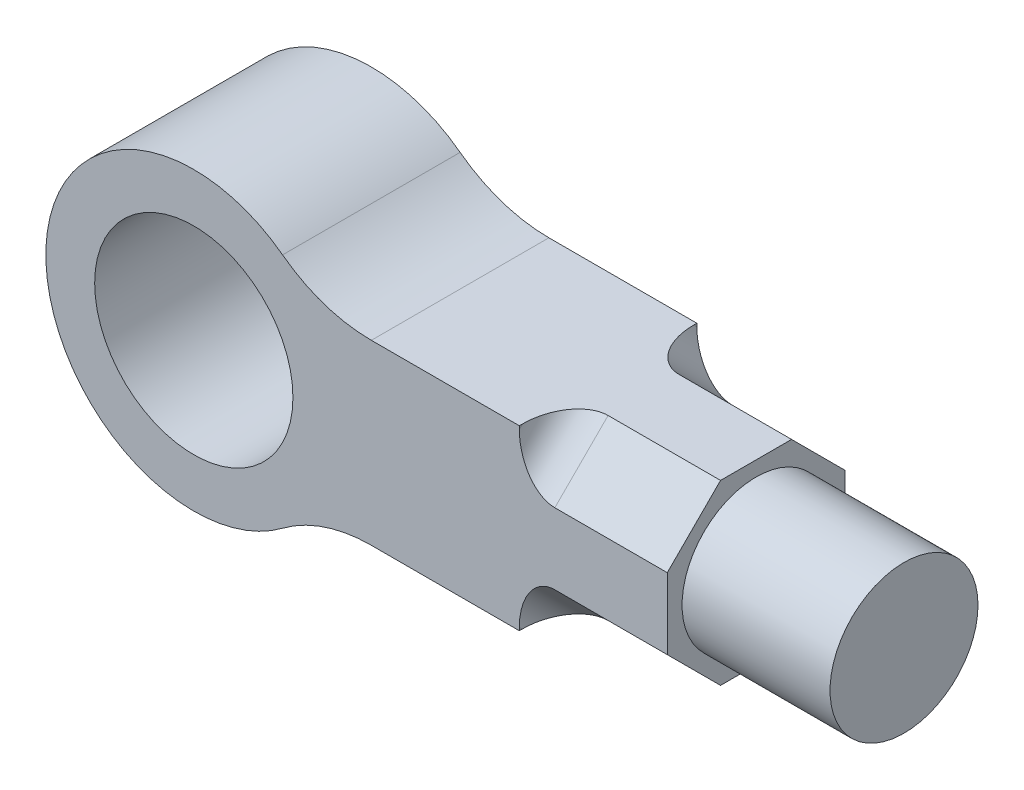
SolidWorks part; units mm, degrees
ref_plane "Front Plane" through (0, 0, 0) normal (0, 0, 1) x (1, 0, 0)
ref_plane "Top Plane" through (0, 0, 0) normal (0, 1, 0) x (1, 0, 0)
ref_plane "Right Plane" through (0, 0, 0) normal (1, 0, 0) x (0, 0, -1)
sketch "Sketch2" plane through (0, 0, 0) normal (0, 0, 1) x (1, 0, 0)
  line L0 (0, 0) -> (119.1651, 0) construction
  line L2 (60, 30) -> (160, 30)
  line L4 (60, -30) -> (160, -30)
  line L5 (160, 30) -> (160, -30)
  circle A0 centre (0, 0) radius 33.5
  arc A1 (30, 40) -> (30, -40) centre (0, 0) ccw
  arc A2 (30, -40) -> (60, -30) centre (60, -80) cw
  arc A3 (60, 30) -> (30, 40) centre (60, 80) cw
  dimension "D1" = 100
  dimension "D2" = 67
  dimension "D5" = 50
  dimension "D3" = 30
  dimension "D4" = 60
  dimension "D6" = 100
extrude "Boss-Extrude1" add sketch "Sketch2" along normal blind 60
sketch "Sketch3" plane through (160, 0, 0) normal (1, 0, 0) x (0, 0, -1)
  line L0 (-18, 30) -> (0, 30)
  line L1 (-60, 30) -> (0, 30) construction
  line L2 (0, 30) -> (0, 12)
  line L3 (0, -30) -> (0, 30) construction
  line L4 (0, 12) -> (-18, 30)
  line L5 (0, -12) -> (0, -30)
  line L6 (0, -30) -> (-18, -30)
  line L7 (-18, -30) -> (0, -12)
  line L8 (-42, -30) -> (-60, -30)
  line L9 (-60, -30) -> (-60, -12)
  line L10 (-60, -12) -> (-42, -30)
  line L11 (-60, 12) -> (-60, 30)
  line L12 (-60, 30) -> (-42, 30)
  line L13 (-42, 30) -> (-60, 12)
  circle A0 centre (-30, 0) radius 25
  line M5 (0, -30) -> (0, 30)
  line M6 (0, 30) -> (-60, 30)
  line M7 (-60, 30) -> (-60, -30)
  line M8 (-60, -30) -> (0, -30)
  dimension "D2" = 50
  dimension "D1" = 30
  dimension "D3" = 18
  dimension "D4" = 18
  dimension "D5" = 4
extrude "Cut-Extrude1" cut sketch "Sketch3" against normal blind 50 contours L13 M6 M7 | L4 M5 M6 | L7 M8 M5 | L10 M7 M8 region at (160, 24, 6) region at (160, 24, 54) region at (160, -24, 6) region at (160, -24, 54)
extrude "Boss-Extrude2" add sketch "Sketch3<3>" along normal blind 50 contours A0 region at (160, 0, 30)
sketch "Sketch3<3>" plane through (160, 0, 0) normal (1, 0, 0) x (0, 0, -1) same geometry as "Sketch3"
fillet "Fillet1" radius 12 4 edges at (110, -21, 9) (110, -21, 51) (110, 21, 9) (110, 21, 51)
